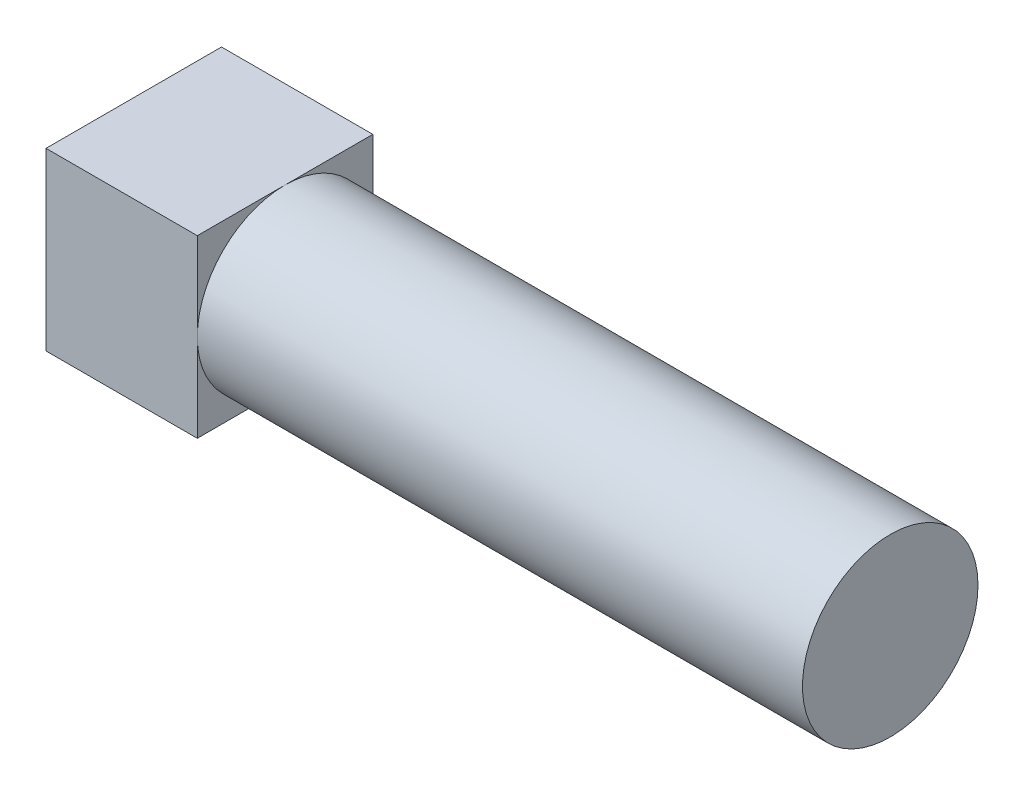
SolidWorks part; units mm, degrees
ref_plane "Front Plane" through (0, 0, 0) normal (0, 0, 1) x (1, 0, 0)
ref_plane "Top Plane" through (0, 0, 0) normal (0, 1, 0) x (1, 0, 0)
ref_plane "Right Plane" through (0, 0, 0) normal (1, 0, 0) x (0, 0, -1)
sketch "Sketch1" plane through (0, 0, 0) normal (1, 0, 0) x (0, 0, -1)
  line L1 (-5.8, 5.8) -> (5.8, 5.8)
  line L2 (-5.8, 5.8) -> (-5.8, -5.8)
  line L3 (-5.8, -5.8) -> (5.8, -5.8)
  line L4 (5.8, 5.8) -> (5.8, -5.8)
  line L5 (-5.8, 5.8) -> (5.8, -5.8) construction
  line L6 (-5.8, -5.8) -> (5.8, 5.8) construction
  point P0 (0, 0)
  dimension "D1" = 11.6
  dimension "D2" = 11.6
extrude "Boss-Extrude1" add sketch "Sketch1" along normal blind 10
sketch "Sketch2" plane through (10, 0, 0) normal (1, 0, 0) x (0, 0, -1)
  circle A0 centre (0, 0) radius 5.8
  dimension "D1" = 11.6
extrude "Boss-Extrude2" add sketch "Sketch2" along normal blind 40
